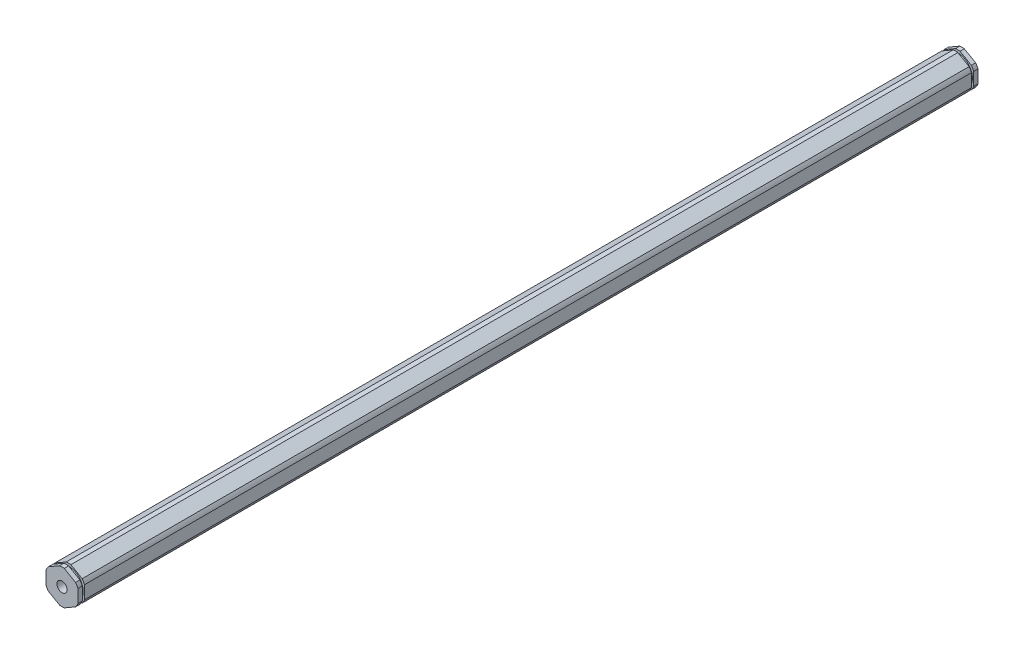
SolidWorks part; units mm, degrees
ref_plane "Front Plane" through (0, 0, 0) normal (0, 0, 1) x (1, 0, 0)
ref_plane "Top Plane" through (0, 0, 0) normal (0, 1, 0) x (1, 0, 0)
ref_plane "Right Plane" through (0, 0, 0) normal (1, 0, 0) x (0, 0, -1)
sketch "Sketch1" plane through (0, 0, 0) normal (0, 0, 1) x (1, 0, 0)
  line L1 (0, 7.3323) -> (-6.35, 3.6662)
  line L2 (-6.35, 3.6662) -> (-6.35, -3.6662)
  line L3 (-6.35, -3.6662) -> (0, -7.3323)
  line L4 (0, -7.3323) -> (6.35, -3.6662)
  line L5 (6.35, -3.6662) -> (6.35, 3.6662)
  line L6 (6.35, 3.6662) -> (0, 7.3323)
  circle A0 centre (0, 0) radius 6.35 construction
  circle A1 centre (0, 0) radius 6.858
  dimension "D1" = 12.7
  dimension "D2" = 13.716
extrude "Boss-Extrude1" add sketch "Sketch1" along normal mid plane 357.759 contours L5 A1 L6 L1 L2 L3 L4 region at (0, 0, 0)
hole_wizard "#10-32 Tapped Hole1" positions "3DSketch1" profile "Sketch2" tap size "#10-32" standard "ANSI Inch"
sketch3d "3DSketch1"
  line L0 (0, 0, 178.8795) -> (0, 0, -178.8795) construction
  line L1 (0, 0, 178.8795) -> (0, 0, -178.8795) construction
  point P0 (0, 0, 178.8795)
  point P4 (0, 0, -178.8795)
sketch "Sketch2" plane through (0, 0, 178.8795) normal (1, 0, 0) x (0, -1, 0)
  line L0 (0, 0) -> (0, 17.5608)
  line L1 (0, 17.5608) -> (2.0193, 16.3474)
  line L2 (2.0193, 16.3474) -> (2.0193, 0)
  line L5 (2.0193, 0) -> (0, 0)
  line L10 (0, 17.5608) -> (-2.0193, 16.3474) construction
  line L11 (0, -6.35) -> (0, 107.95) construction
  dimension "Tap Drill Dia." = 4.0386
  dimension "Tap Drill Depth" = 16.3474
  dimension "Drill Angle" = 118
cosmetic thread "Hole Thread1" parameters "D1"=13.97, "D2"=4.826
cosmetic thread "Hole Thread2" parameters "D1"=13.97, "D2"=4.826
sketch "Sketch5" plane through (0, 0, 0) normal (1, 0, 0) x (0, 0, -1)
  line L0 (178.8795, 6.858) -> (-178.8795, 6.858) construction
  line L1 (-177.165, 6.858) -> (-176.276, 6.858)
  line L2 (-177.165, 6.858) -> (-177.165, 5.8547)
  line L3 (-177.165, 5.8547) -> (-176.276, 5.8547)
  line L4 (-176.276, 6.858) -> (-176.276, 5.8547)
  line L5 (-165.0472, 0) -> (-158.8423, 0) construction
  dimension "D1" = 5.8547
  dimension "D2" = 0.889
  dimension "D3" = 1.7145
revolve "Cut-Revolve1" cut sketch "Sketch5" angle 360 about L5
mirror "Mirror1" about plane through (0, 0, 0) normal (0, 0, 1) of "Cut-Revolve1"
